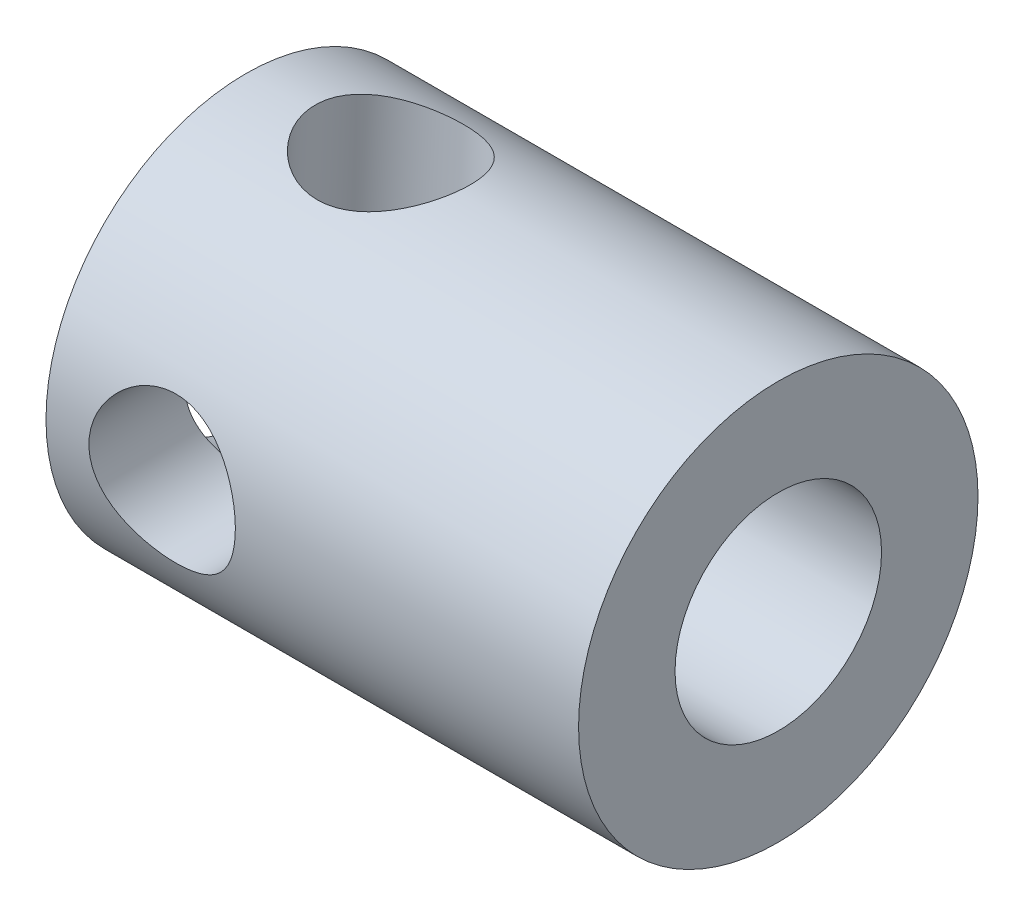
SolidWorks part; units mm, degrees
ref_plane "Alzado" through (0, 0, 0) normal (0, 0, 1) x (1, 0, 0)
ref_plane "Planta" through (0, 0, 0) normal (0, 1, 0) x (1, 0, 0)
ref_plane "Vista lateral" through (0, 0, 0) normal (1, 0, 0) x (0, 0, -1)
sketch "Croquis1" plane through (0, 0, 0) normal (1, 0, 0) x (0, 0, -1)
  circle A0 centre (0, 0) radius 7.5
  circle A1 centre (0, 0) radius 3.8779
  dimension "D1" = 15
extrude "Saliente-Extruir1" add sketch "Croquis1" along normal blind 20
hole_wizard "Taladro de margen para M51" positions "Croquis3D1" profile "Croquis2" hole size "M5" standard "Ansi Metric" end condition through all
sketch3d "Croquis3D1"
  point P0 (5.0641, 7.4894, -0.3993)
  point P2 (4.3598, 0.0024, 7.5)
sketch "Croquis2" plane through (5.0641, 7.4894, -0.3993) normal (1, 0, 0) x (0, 0.0532, 0.9986)
  line L0 (0, 0) -> (0, 15.3887)
  line L1 (0, 15.3887) -> (2.75, 15.3887)
  line L2 (2.75, 15.3887) -> (2.75, 0)
  line L5 (2.75, 0) -> (0, 0)
  line L11 (0, -6.35) -> (0, 107.95) construction
  dimension "Diámetro de taladro hasta el siguiente" = 5.5
  dimension "Profundidad de taladro hasta el siguiente" = 15.3887
